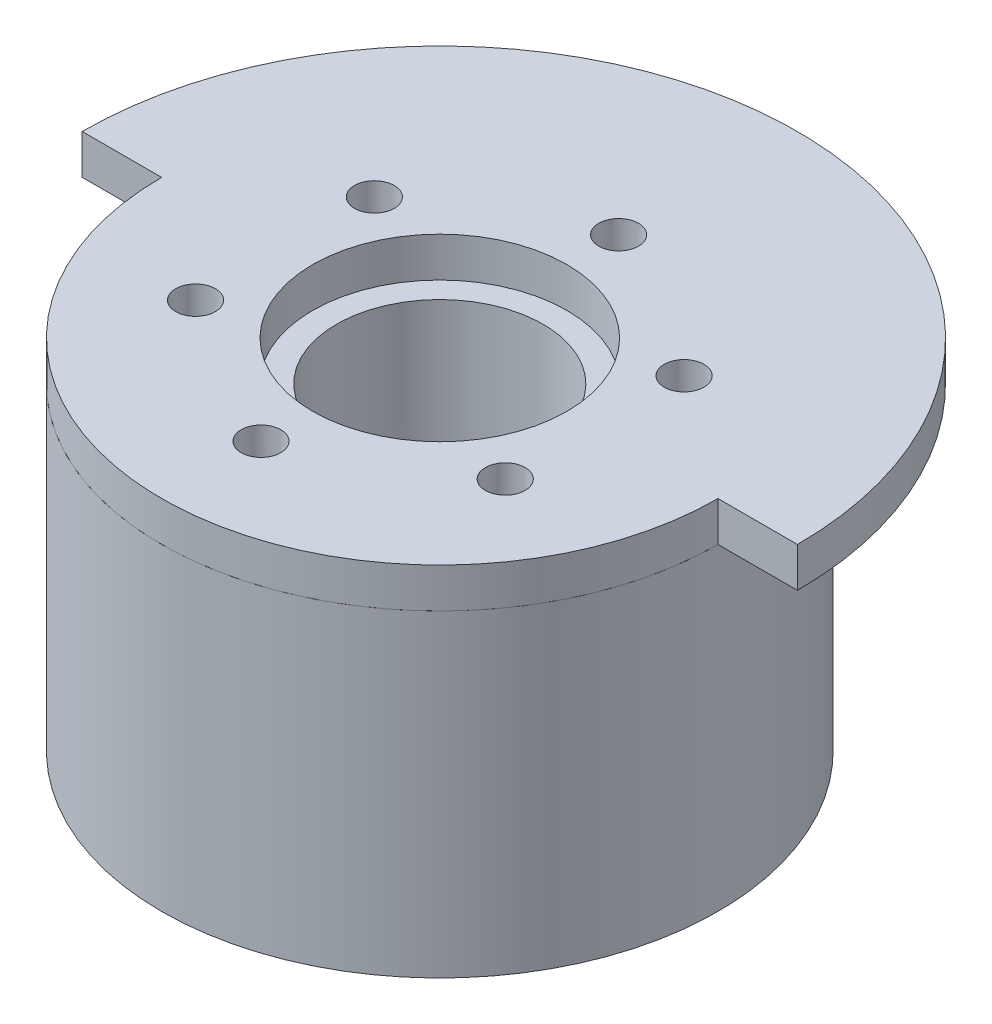
SolidWorks part; units mm, degrees
ref_plane "Front Plane" through (0, 0, 0) normal (0, 0, 1) x (1, 0, 0)
ref_plane "Top Plane" through (0, 0, 0) normal (0, 1, 0) x (1, 0, 0)
ref_plane "Right Plane" through (0, 0, 0) normal (1, 0, 0) x (0, 0, -1)
sketch "Sketch1" plane through (0, 0, 0) normal (0, 1, 0) x (1, 0, 0)
  circle A0 centre (0, 0) radius 35
  circle A1 centre (0, 0) radius 22.5 construction
  circle A2 centre (0, 0) radius 5
  circle A3 centre (0, 22.5) radius 2.5
  circle A4 centre (19.4856, 11.25) radius 2.5
  circle A5 centre (19.4856, -11.25) radius 2.5
  circle A6 centre (0, -22.5) radius 2.5
  circle A7 centre (-19.4856, -11.25) radius 2.5
  circle A8 centre (-19.4856, 11.25) radius 2.5
  point P19 (0, 0)
  dimension "D1" = 70
  dimension "D2" = 10
  dimension "D3" = 45
  dimension "D4" = 5
  dimension "D5" = 6
extrude "Boss-Extrude1" add sketch "Sketch1" along normal blind 40
sketch "Sketch2" plane through (0, 0, 0) normal (0, -1, 0) x (1, 0, 0)
  circle A0 centre (0, 0) radius 16
  dimension "D1" = 32
extrude "Cut-Extrude1" cut sketch "Sketch2" against normal blind 5
sketch "Sketch5" plane through (0, 40, 0) normal (0, 1, 0) x (1, 0, 0)
  circle A0 centre (0, 0) radius 13
  dimension "D1" = 26
extrude "Cut-Extrude2" cut sketch "Sketch5" against normal up to surface (35 mm away) up to face at (0, 5, -5)
sketch "Sketch6" plane through (0, 40, 0) normal (0, 1, 0) x (1, 0, 0)
  line L1 (-35, 0) -> (-35, -35)
  line L2 (-35, -35) -> (35, -35)
  line L3 (35, -35) -> (35, 0)
  line L4 (35, 0) -> (45, 0)
  line L5 (-45, 0) -> (-35, 0)
  arc A3 (45, 0) -> (-45, 0) centre (0, 0) ccw
  circle A4 centre (0, 22.5) radius 2.5
  circle A5 centre (19.4856, 11.25) radius 2.5
  circle A6 centre (19.4856, -11.25) radius 2.5
  circle A7 centre (0, -22.5) radius 2.5
  circle A8 centre (-19.4856, -11.25) radius 2.5
  circle A9 centre (-19.4856, 11.25) radius 2.5
  circle A10 centre (0, 22.5) radius 2.5 construction
  circle A11 centre (0, 0) radius 13
  circle A12 centre (0, 0) radius 13 construction
  circle A14 centre (0, 0) radius 35 construction
  circle M4 centre (0, 0) radius 13
  circle M7 centre (0, 22.5) radius 2.5
  circle M8 centre (0, 0) radius 35
  circle M9 centre (19.4856, 11.25) radius 2.5
  circle M11 centre (-19.4856, 11.25) radius 2.5
  dimension "D1" = 90
extrude "Boss-Extrude2" add sketch "Sketch6" along normal blind 5 separate body contours A3 M8 | M8 M4 M11 M9 M7 region at (-40, 40, -1.0062) region at (0, 40, -34.0101)
sketch "Sketch7" plane through (0, 45, 0) normal (0, 1, 0) x (1, 0, 0)
  circle A0 centre (0, 0) radius 16
  circle A1 centre (0, 0) radius 16 construction
extrude "Cut-Extrude3" cut sketch "Sketch7" against normal blind 5
